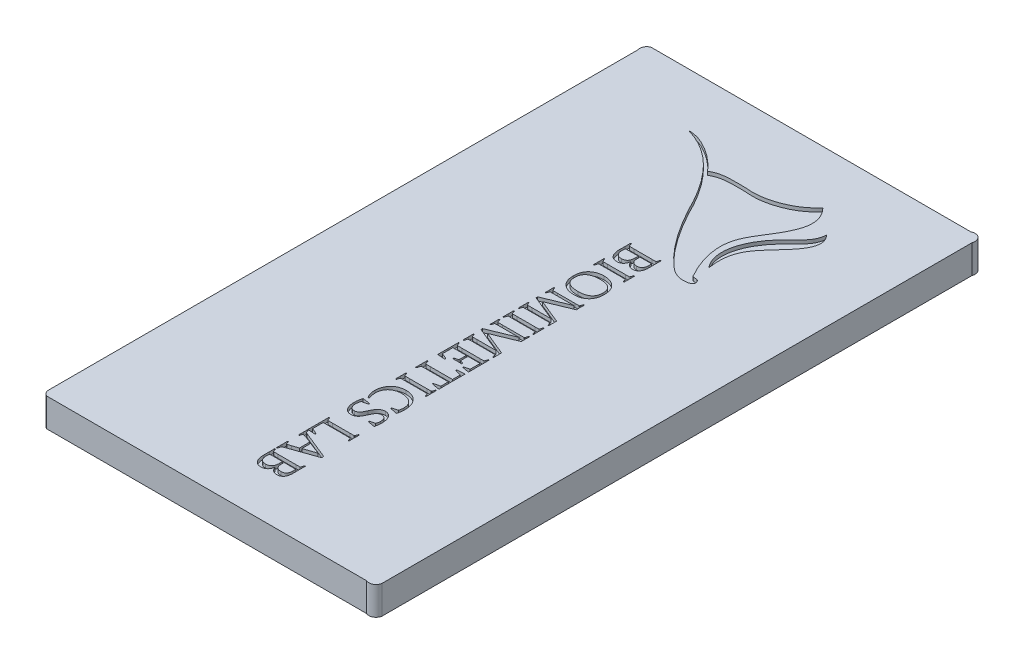
SolidWorks part; units mm, degrees
ref_plane "Front Plane" through (0, 0, 0) normal (0, 0, 1) x (1, 0, 0)
ref_plane "Top Plane" through (0, 0, 0) normal (0, 1, 0) x (1, 0, 0)
ref_plane "Right Plane" through (0, 0, 0) normal (1, 0, 0) x (0, 0, -1)
sketch "Sketch1" plane through (0, 0, 0) normal (0, 1, 0) x (1, 0, 0)
  line L0 (-18, 37.5) -> (-18, -37)
  line L1 (-18, -37) -> (18.8, -37)
  line L2 (23.9, -41.5) -> (23.9, 41.5)
  line L3 (22.5, 42.75) -> (-22.5, 42.75)
  line L4 (-23.1, 41.5) -> (-23.1, -41.5)
  line L5 (-22.5, -42.25) -> (22.5, -42.25)
  line L6 (18.8, 37.5) -> (18.8, -37)
  line L7 (-18, 37.5) -> (18.8, 37.5)
  arc A0 (23.9, 41.5) -> (22.5, 42.75) centre (22.9699, 41.8673) ccw
  arc A1 (-22.5, 42.75) -> (-23.1, 41.5) centre (-22.1503, 41.8131) ccw
  arc A2 (-23.1, -41.5) -> (-22.5, -42.25) centre (-22.1151, -41.3271) ccw
  arc A3 (22.5, -42.25) -> (23.9, -41.5) centre (22.913, -41.3393) ccw
  dimension "D1" = 36.8
  dimension "D2" = 47
  dimension "D3" = 74.5
  dimension "D4" = 85
  dimension "D5" = 37.5
  dimension "D6" = 18
  dimension "D7" = 5.1
  dimension "D8" = 5.25
  dimension "D9" = 5.1
extrude "Boss-Extrude1" add sketch "Sketch1" along normal blind 4 contours L7 L0 L1 L6 | L5 A3 L2 A0 L3 A1 L4 A2 L0 L7 L6 L1 region at (0.4, 0, -0.25) region at (22.9254, 0, 41.3625)
extrude "Boss-Extrude2" add sketch "Sketch1<3>" against normal blind 4 contours L7 L0 L1 L6 region at (0.4, 0, -0.25)
sketch "Sketch1<3>" plane through (0, 0, 0) normal (0, 1, 0) x (1, 0, 0) same geometry as "Sketch1"
sketch "Sketch2" plane through (0, -4, 0) normal (0, -1, 0) x (1, 0, 0)
  line L0 (-18, 37) -> (18.8, 37) construction
  line L1 (-16.25, 35) -> (16.25, 35)
  line L2 (-16.25, 35) -> (-16.25, -35)
  line L3 (-16.25, -35) -> (16.25, -35)
  line L4 (16.25, 35) -> (16.25, -35)
  line L5 (-16.25, 35) -> (16.25, -35) construction
  line L6 (-16.25, -35) -> (16.25, 35) construction
  line L7 (-5.5, 37) -> (5.5, 37)
  line L8 (-5.5, 37) -> (-5.5, 35)
  line L9 (-5.5, 35) -> (5.5, 35)
  line L10 (5.5, 37) -> (5.5, 35)
  line L11 (-18, -37.5) -> (-18, 37) construction
  point P0 (0, 0)
  line M11 (18.8, 37) -> (-18, 37)
  dimension "D1" = 32.5
  dimension "D2" = 70
  dimension "D3" = 11
  dimension "D4" = 12.5
extrude "Cut-Extrude1" cut sketch "Sketch2" against normal blind 5 contours L4 L1 L2 L3 region at (0, -4, 0)
extrude "Cut-Extrude2" cut sketch "Sketch2<3>" against normal blind 4 contours L10 L8 L1 M11 region at (0, -4, 36)
sketch "Sketch2<3>" plane through (0, -4, 0) normal (0, -1, 0) x (1, 0, 0) same geometry as "Sketch2"
fillet "Fillet1" radius 1 10 edges at (-16.25, -1.5, 35) (16.25, -1.5, 35) (-16.25, -1.5, -35) (16.25, -1.5, -35) (5.5, -2, 37) (-5.5, -2, 37) (18.8, -2, 37) (-18, -2, 37) (-18, -2, -37.5) (18.8, -2, -37.5)
sketch "Sketch3" plane through (0, 4, 0) normal (0, 1, 0) x (1, 0, 0)
  line L0 (4.0436, 14.6055) -> (4.0436, 99.6055) construction
  line L1 (-40.1222, 28.6634) -> (-40.1222, -56.3366) construction
  line L2 (0, 42.75) -> (0, -42.25) construction
  line L3 (22.5, 42.75) -> (-22.5, 42.75) construction
  line L4 (-22.5, -42.25) -> (22.5, -42.25) construction
  line L5 (347.2017, -160.3518) -> (347.2017, -1013.6851) construction
  spline S0 degree 3 poles (9.1568, 35.2599) (8.0031, 33.9132) (5.583, 32.5884) (2.6394, 32.138) (1.1789, 32.3002) (-0.6371, 32.2565) (-2.2159, 32.3562) (-3.3949, 31.6186) knots 0 0 0 0 0.388867 0.595687 0.651024 0.715437 1 1 1 1
  spline S1 degree 3 poles (-3.3949, 31.6186) (-4.3019, 32.6572) (-6.2204, 34.2808) (-8.5856, 35.2739) (-9.7506, 35.2599) knots 0 0 0 0 0.545718 1 1 1 1
  spline S2 degree 3 poles (-9.7506, 35.2599) (-5.0425, 34.0182) (-2.0065, 29.6086) (0, 25.4878) knots 0 0 0 0 1 1 1 1
  spline S3 degree 3 poles (0, 25.4878) (1.5164, 22.7314) (3.7799, 19.191) (7.4587, 16.2849) (9.5346, 16.8221) (9.1512, 17.9528) (8.3676, 17.5244) (8.2451, 18.0338) knots 0 0 0 0 0.617672 0.826885 0.894883 0.931266 1 1 1 1
  spline S4 degree 3 poles (8.2451, 18.0338) (7.1433, 19.928) (5.805, 24.0285) (9.2791, 29.2127) (11.3853, 33.0287) (9.1568, 35.2599) knots 0 0 0 0 0.37408 0.590964 1 1 1 1
  spline S5 degree 3 poles (12.709, 32.2271) (12.7205, 30.9412) (11.3016, 29.5997) (9.3318, 27.6234) (7.3827, 24.6462) (7.118, 21.5339) (8.4353, 19.9544) knots 0 0 0 0 0.249686 0.397227 0.599239 1 1 1 1
  spline S6 degree 3 poles (12.709, 32.2271) (14.0934, 30.8562) (11.0722, 26.1986) (7.746, 24.2046) (8.4353, 19.9544) knots 0 0 0 0 0.348722 1 1 1 1
  text T0 "BIOMIMETICS LAB    " font "Constantia" height 4.3
  dimension "D1" = 19.5042
extrude "Cut-Extrude3" cut sketch "Sketch3" against normal blind 0.5
sketch "Sketch4" plane through (0, -4, 0) normal (0, -1, 0) x (1, 0, 0)
  line L1 (18.8, -12.5) -> (16.25, -12.5)
  line L2 (18.8, -12.5) -> (18.8, 12.5)
  line L3 (18.8, 12.5) -> (16.25, 12.5)
  line L4 (16.25, -12.5) -> (16.25, 12.5)
  line L12 (17.8, 37) -> (6.5, 37)
  line L13 (5.5, 36) -> (5.5, 35)
  line L14 (5.5, 35) -> (15.25, 35)
  line L15 (16.25, 34) -> (16.25, -34)
  line L16 (15.25, -35) -> (-15.25, -35)
  line L17 (-16.25, -34) -> (-16.25, 34)
  line L18 (-15.25, 35) -> (-5.5, 35)
  line L19 (-5.5, 35) -> (-5.5, 36)
  line L20 (-6.5, 37) -> (-17, 37)
  line L21 (-18, 36) -> (-18, -36.5)
  line L22 (-17, -37.5) -> (17.8, -37.5)
  line L23 (18.8, -36.5) -> (18.8, 36)
  line L24 (17.8, 37) -> (6.5, 37)
  line L25 (5.5, 36) -> (5.5, 35)
  line L26 (5.5, 35) -> (15.25, 35)
  line L27 (16.25, 34) -> (16.25, -34)
  line L28 (15.25, -35) -> (-15.25, -35)
  line L29 (-16.25, -34) -> (-16.25, 34)
  line L30 (-15.25, 35) -> (-5.5, 35)
  line L31 (-5.5, 35) -> (-5.5, 36)
  line L32 (-6.5, 37) -> (-17, 37)
  line L33 (-18, 36) -> (-18, -36.5)
  line L34 (-17, -37.5) -> (17.8, -37.5)
  line L35 (18.8, -36.5) -> (18.8, 36)
  arc A10 (6.5, 37) -> (5.5, 36) centre (6.5, 36) ccw
  arc A11 (16.25, 34) -> (15.25, 35) centre (15.25, 34) ccw
  arc A12 (15.25, -35) -> (16.25, -34) centre (15.25, -34) ccw
  arc A13 (-16.25, -34) -> (-15.25, -35) centre (-15.25, -34) ccw
  arc A14 (-15.25, 35) -> (-16.25, 34) centre (-15.25, 34) ccw
  arc A15 (-5.5, 36) -> (-6.5, 37) centre (-6.5, 36) ccw
  arc A16 (-17, 37) -> (-18, 36) centre (-17, 36) ccw
  arc A17 (-18, -36.5) -> (-17, -37.5) centre (-17, -36.5) ccw
  arc A18 (17.8, -37.5) -> (18.8, -36.5) centre (17.8, -36.5) ccw
  arc A19 (18.8, 36) -> (17.8, 37) centre (17.8, 36) ccw
  arc A20 (6.5, 37) -> (5.5, 36) centre (6.5, 36) ccw
  arc A21 (16.25, 34) -> (15.25, 35) centre (15.25, 34) ccw
  arc A22 (15.25, -35) -> (16.25, -34) centre (15.25, -34) ccw
  arc A23 (-16.25, -34) -> (-15.25, -35) centre (-15.25, -34) ccw
  arc A24 (-15.25, 35) -> (-16.25, 34) centre (-15.25, 34) ccw
  arc A25 (-5.5, 36) -> (-6.5, 37) centre (-6.5, 36) ccw
  arc A26 (-17, 37) -> (-18, 36) centre (-17, 36) ccw
  arc A27 (-18, -36.5) -> (-17, -37.5) centre (-17, -36.5) ccw
  arc A28 (17.8, -37.5) -> (18.8, -36.5) centre (17.8, -36.5) ccw
  arc A29 (18.8, 36) -> (17.8, 37) centre (17.8, 36) ccw
  point P24 (17.525, 12.5)
  line M32 (16.25, 34) -> (16.25, -34)
  line M47 (18.8, -36.5) -> (18.8, 36)
  dimension "D2" = 25
  dimension "D3" = 25
  dimension "D1" = 0
extrude "Cut-Extrude4" cut sketch "Sketch4" against normal up to surface (4 mm away) contours L3 L1 M47 M32 region at (17.525, -4, 0) up to face at (0.2342, 0, -0.1483)
